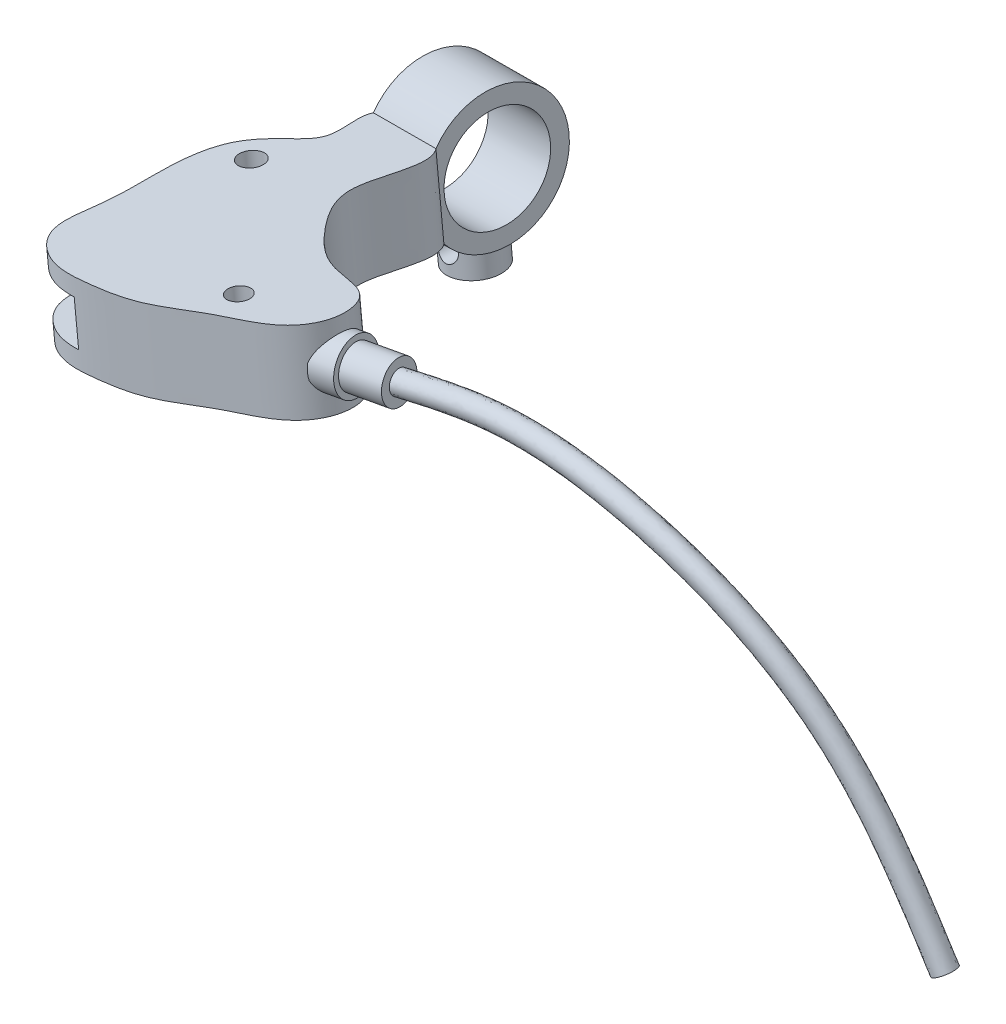
SolidWorks part; units mm, degrees
material "Aleación 6061"
ref_plane "Alzado" through (0, 0, 0) normal (0, 0, 1) x (1, 0, 0)
ref_plane "Planta" through (0, 0, 0) normal (0, 1, 0) x (1, 0, 0)
ref_plane "Vista lateral" through (0, 0, 0) normal (1, 0, 0) x (0, 0, -1)
sketch3d "Sk_Abrazadera"
  line L0 (231.9631, 41.8477, -24.5933) -> (247.8038, 40.2316, -26.1614)
  dimension "D1" = 16
sweep "Abrazadera" add path "Sk_Abrazadera" circular profile diameter 30 parameters "D3"=30
sketch3d "Sk_Orejeta_tornillo"
  line L0 (238.8685, 31.0913, -25.3774) -> (237.7521, 20.1481, -25.3774)
  dimension "D1" = 11
sweep "Orejeta_tornillo" add path "Sk_Orejeta_tornillo" circular profile diameter 12 parameters "D3"=12
sketch3d "Sk_puntos_Plano_maneta"
  point P0 (247.8038, 40.2316, -26.1614)
  point P1 (297.3062, 35.1814, -31.0616)
  point P2 (252.6788, 39.7343, 23.5979)
ref_plane "Plano_maneta" through (6.6148, 64.8378, 0) normal (-0.1015, -0.9948, 0) x (-0.9948, 0.1015, 0)
sketch "Sk_Cuerpo" plane through (6.6148, 64.8378, 0) normal (-0.1015, -0.9948, 0) x (-0.9948, 0.1015, 0)
  spline S0 degree 3 poles (-247.7512, 19.043) (-219.2378, 14.8287) (-233.0703, -3.9125) (-224.3795, -16.5455) (-215.9984, -24.7968) (-204.0634, -25.3721) (-202.2986, -34.6945) (-207.5963, -43.1878) (-219.6304, -45.8033) (-230.7037, -51.8113) (-242.0526, -52.3892) (-251.9269, -52.068) (-260.8099, -44.2141) (-257.2989, -31.2772) (-258.4685, -18.7548) (-256.3278, -6.3369) (-249.6245, -0.5608) (-242.3483, 4.3803) (-247.7512, 19.043) (-219.2378, 14.8287) (-233.0703, -3.9125) knots -0.159656 -0.128106 -0.078835 0 0.088689 0.146149 0.210392 0.261833 0.292995 0.330519 0.398969 0.465074 0.515322 0.564655 0.608518 0.667849 0.74192 0.801862 0.840344 0.871894 0.921165 1 1.088689 1.146149 1.210392 only from (-227.6941, 12.6511) to (-227.6941, 12.6511)
extrude "Cuerpo" add sketch "Sk_Cuerpo" along normal mid plane 18
sketch3d "Sk_Contratuerca"
  line L0 (211.6817, 43.9168, 33.8823) -> (206.237, 44.4723, 33.3374)
  dimension "D1" = 5.5
sweep "Contratuerca" add path "Sk_Contratuerca" circular profile diameter 11.5 parameters "D3"=11.5
sketch3d "Sk_Regulador_cable"
  line L0 (206.237, 44.4723, 33.3374) -> (197.3275, 45.3812, 32.4458)
  dimension "D1" = 9
sweep "Regulador_cable" add path "Sk_Regulador_cable" circular profile diameter 9 parameters "D3"=9
sketch3d "Sk_Funda_cable"
  spline S0 degree 3 poles (198.3175, 45.2802, 32.5448) (191.4116, 46.327, 31.8139) (173.7972, 48.997, 29.9494) (141.0079, 41.8099, 27.8947) (109.7438, 15.0723, 18.9485) (95.1692, -10.7432, 17.8995) (87.7659, -23.8565, 17.3666) knots 0 0 0 0 0.147729 0.376804 0.683439 1 1 1 1
sweep "Funda_cable" add path "Sk_Funda_cable" circular profile diameter 5 parameters "D3"=5
sketch "Sk_Ranura_palanca" plane through (6.6148, 64.8378, 0) normal (-0.1015, -0.9948, 0) x (-0.9948, 0.1015, 0)
  spline S0 degree 3 poles (-232.2258, -11.9649) (-237.8557, 2.2413) (-250.578, 5.8543) (-267.486, 1.6073) (-260.9854, -24.5451) (-278.9085, -54.2558) (-243.0351, -59.4222) (-243.6976, -37.6813) (-232.7822, -26.7229) (-232.2258, -11.9649) (-237.8557, 2.2413) (-250.578, 5.8543) knots -0.266705 -0.195409 -0.106133 0 0.065032 0.133713 0.287289 0.485075 0.606236 0.733295 0.804591 0.893867 1 1.065032 1.133713 1.287289 only from (-240.8124, 1.8849) to (-240.8124, 1.8849)
extrude "Ranura_palanca" cut sketch "Sk_Ranura_palanca" against normal mid plane 10
sketch3d "Sk_Agujero_pivote"
  line L0 (253.0675, 27.6323, 8.3663) -> (255.5034, 51.5084, 8.3663)
  dimension "D1" = 24
sweep "Agujero_pivote" cut path "Sk_Agujero_pivote" circular profile diameter 5.5 parameters "D3"=5.5
sketch3d "Sk_Agujero_abrazadera"
  line L0 (230.973, 41.9487, -24.4953) -> (248.7939, 40.1306, -26.2594)
  dimension "D1" = 18
sweep "Agujero_abrazadera" cut path "Sk_Agujero_abrazadera" circular profile diameter 22.2 parameters "D3"=22.2
sketch3d "Sk_Agujero_tornillo_M5"
  line L0 (237.3821, 25.2118, -34.334) -> (239.1371, 25.0328, -16.4207)
  dimension "D1" = 18
sweep "Agujero_tornillo_M5" cut path "Sk_Agujero_tornillo_M5" circular profile diameter 5.5 parameters "D3"=5.5
sketch3d "Sk_Paso_cable_cuerpo"
  line L0 (208.7119, 44.2198, 33.5851) -> (247.241, 40.289, 19.112)
  dimension "D1" = 41.3451
sweep "Paso_cable_cuerpo" cut path "Sk_Paso_cable_cuerpo" circular profile diameter 2.5 parameters "D3"=2.5
sketch3d "Sk_Aligerado"
  line L0 (225.007, 30.4951, 39.2795) -> (227.4429, 54.3711, 39.2795)
  dimension "D1" = 24
sweep "Aligerado" cut path "Sk_Aligerado" circular profile diameter 5 parameters "D3"=5
mirror "Simetria_lado_izq" about plane through (0, 0, 0) normal (1, 0, 0) of bodies 112
delete or keep bodies "Borrar_original_dcho" type delete bodies bodies 112
